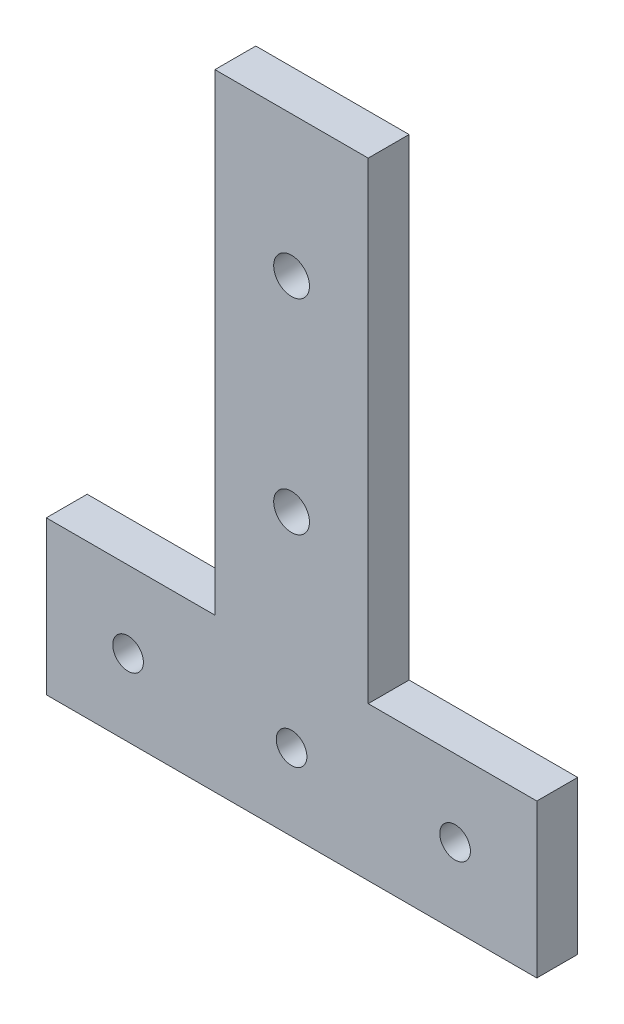
SolidWorks part; units mm, degrees
ref_plane "前视基准面" through (0, 0, 0) normal (0, 0, 1) x (1, 0, 0)
ref_plane "上视基准面" through (0, 0, 0) normal (0, 1, 0) x (1, 0, 0)
ref_plane "右视基准面" through (0, 0, 0) normal (1, 0, 0) x (0, 0, -1)
other "Configuration Table"
sketch "草图1" plane through (0, 0, 0) normal (0, 0, 1) x (1, 0, 0)
  line L0 (-49.7112, 0) -> (49.7112, 0) construction
  line L1 (0, 0) -> (0, 42.7175) construction
  line L2 (7.5, 7.5) -> (24, 7.5)
  line L3 (24, 7.5) -> (24, -7.5)
  line L4 (24, -7.5) -> (-24, -7.5)
  line L5 (7.5, 7.5) -> (7.5, 53.7328)
  line L6 (7.5, 53.7328) -> (-7.5, 53.7328)
  line L7 (-7.5, 7.5) -> (-7.5, 53.7328)
  line L8 (-24, 7.5) -> (-24, -7.5)
  line L9 (-7.5, 7.5) -> (-24, 7.5)
  line L10 (-24, 15.3135) -> (-21.6322, 15.3135)
  circle A0 centre (16, 0) radius 1.5
  circle A1 centre (0, 0) radius 1.5
  circle A2 centre (-16, 0) radius 1.5
  circle A3 centre (0, 20) radius 1.75
  circle A4 centre (0, 40) radius 1.75
  point P17 (0, 53.7328)
  point P19 (0, -7.5)
  dimension "D5" = 3
  dimension "D6" = 3
  dimension "D7" = 3.5
  dimension "D9" = 3.5
  dimension "D1" = 15
  dimension "D2" = 15
  dimension "D3" = 48
  dimension "D4" = 32
  dimension "D8" = 20
  dimension "D10" = 20
extrude "凸台-拉伸1" add sketch "草图1" along normal blind 4 contours L7 L9 L8 L4 L3 L2 L5 L6 A4 A3 A0 A1 A2 region at (0, 15.0432, 0)
